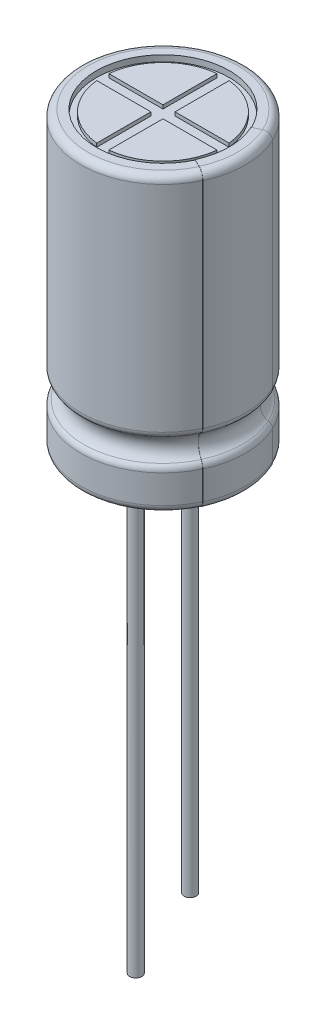
SolidWorks part; units mm, degrees
note: The reader was unsure of these and kept them because the rebuilt part matched: shared geometry of "Sketch7<4>".
ref_plane "Front Plane" through (0, 0, 0) normal (0, 0, 1) x (1, 0, 0)
ref_plane "Top Plane" through (0, 0, 0) normal (0, 1, 0) x (1, 0, 0)
ref_plane "Right Plane" through (0, 0, 0) normal (1, 0, 0) x (0, 0, -1)
sketch "Sketch1" plane through (0, 0, 0) normal (0, 0, 1) x (1, 0, 0)
  line L8 (0, 0.6) -> (2.8, 0.6)
  line L9 (2.8, 0.6) -> (2.8, 0.4)
  line L10 (2.8, 0.4) -> (3.1, 0.4)
  line L11 (3.4, 0.7) -> (3.4, 1.8735)
  line L12 (3.1, 12.5) -> (2.75, 12.5)
  line L13 (2.75, 12.5) -> (2.75, 12.25)
  line L14 (2.75, 12.25) -> (0, 12.25)
  line L15 (0, 12.25) -> (0, 0.6)
  line L16 (1.2518, 2.6) -> (5.492, 2.6) construction
  line L17 (3.4, 3.3265) -> (3.4, 12.2)
  arc A0 (3.1, 0.4) -> (3.4, 0.7) centre (3.1, 0.7) ccw
  arc A1 (3.4, 12.2) -> (3.1, 12.5) centre (3.1, 12.2) ccw
  arc A2 (3.2701, 3.0794) -> (3.2701, 2.1206) centre (3.6, 2.6) ccw
  arc A3 (3.4, 1.8735) -> (3.2701, 2.1206) centre (3.1, 1.8735) ccw
  arc A4 (3.4, 3.3265) -> (3.2701, 3.0794) centre (3.1, 3.3265) cw
  dimension "D8" = 0.3
  dimension "D11" = 1.1639
  dimension "D12" = 0.3
  dimension "D1" = 11.65
  dimension "D2" = 0.2
  dimension "D3" = 0.6
  dimension "D4" = 2.75
  dimension "D5" = 0.65
  dimension "D6" = 0.25
  dimension "D7" = 0.6
  dimension "D9" = 2.2
  dimension "D10" = 3.6
revolve "Revolve1" add sketch "Sketch1" angle 360 about L15
sketch "Sketch2" plane through (0, 12.25, 0) normal (0, 1, 0) x (1, 0, 0)
  line L0 (-0.25, 0.25) -> (-0.25, 2.4875)
  line L2 (0.25, -2.4875) -> (0.25, -0.25)
  line L4 (-0.25, -2.4875) -> (-0.25, -0.25)
  line L5 (0.25, 0.25) -> (0.25, 2.4875)
  line L7 (2.4875, -0.25) -> (0.25, -0.25)
  line L9 (2.4875, 0.25) -> (0.25, 0.25)
  line L13 (-0.25, -0.25) -> (-2.4875, -0.25)
  line L16 (-0.25, 0.25) -> (-2.4875, 0.25)
  arc A0 (0.25, -2.4875) -> (2.4875, -0.25) centre (0, 0) ccw
  arc A1 (2.4875, 0.25) -> (0.25, 2.4875) centre (0, 0) ccw
  arc A2 (-0.25, 2.4875) -> (-2.4875, 0.25) centre (0, 0) ccw
  arc A3 (-2.4875, -0.25) -> (-0.25, -2.4875) centre (0, 0) ccw
  dimension "D3" = 2.5
  dimension "D1" = 0.5
  dimension "D2" = 0.5
extrude "Boss-Extrude1" add sketch "Sketch2" along normal blind 0.15 separate body
sketch "Sketch3" plane through (0, 0.6, 0) normal (0, -1, 0) x (1, 0, 0)
  circle A0 centre (0, 0) radius 1.8
  ellipse E0 centre (0, 0) end of major axis (-1.67, 0) minor radius 0.9
  dimension "D1" = 3.6
extrude "Boss-Extrude2" add sketch "Sketch3" along normal blind 0.6 separate body
sketch "Sketch4" plane through (0, 0.6, 0) normal (0, -1, 0) x (1, 0, 0)
sketch "Sketch5" plane through (0, 0, 0) normal (0, 0, 1) x (1, 0, 0)
  line L8 (2.75, 12.5) -> (3.1, 12.5)
  line L10 (3.4, 3.3265) -> (3.4, 12.2) construction
  line L11 (3.4, 12.2) -> (3.4, 3.3265)
  line L12 (2.75, 12.5) -> (2.8, 0.4)
  line L13 (2.8, 0.4) -> (3.1, 0.4)
  line L14 (0, 0) -> (0, 15.0032) construction
  line L15 (3.41, 12.2) -> (3.41, 3.3265)
  line L16 (3.4, 0.7) -> (3.4, 1.8735)
  line L17 (3.41, 0.7) -> (3.41, 1.8735)
  line L18 (2.79, 0.39) -> (3.1, 0.39)
  line L19 (2.74, 12.51) -> (2.79, 0.39)
  line L20 (2.74, 12.51) -> (3.1, 12.51)
  arc A5 (3.1, 12.5) -> (3.4, 12.2) centre (3.1, 12.2) cw
  arc A6 (3.1, 0.4) -> (3.4, 0.7) centre (3.1, 0.7) ccw construction
  arc A7 (3.4, 1.8735) -> (3.2701, 2.1206) centre (3.1, 1.8735) ccw
  arc A8 (3.4, 3.3265) -> (3.2701, 3.0794) centre (3.1, 3.3265) cw
  arc A9 (3.2701, 3.0794) -> (3.2701, 2.1206) centre (3.6, 2.6) ccw
  arc A10 (3.4, 0.7) -> (3.1, 0.4) centre (3.1, 0.7) cw
  arc A11 (3.1, 12.51) -> (3.41, 12.2) centre (3.1, 12.2) cw
  arc A12 (3.41, 3.3265) -> (3.2757, 3.0712) centre (3.1, 3.3265) cw
  arc A13 (3.2757, 3.0712) -> (3.2757, 2.1288) centre (3.6, 2.6) ccw
  arc A14 (3.41, 1.8735) -> (3.2757, 2.1288) centre (3.1, 1.8735) ccw
  arc A15 (3.41, 0.7) -> (3.1, 0.39) centre (3.1, 0.7) cw
  dimension "D1" = 0.01
revolve "Revolve3" add sketch "Sketch5" angle 25 about L14
sketch "Sketch7" plane through (0, 0.6, 0) normal (0, -1, 0) x (1, 0, 0)
  line L0 (-1.4523, 0) -> (1.4342, 0) construction
  line L1 (0, 0) -> (0, 0.7626) construction
  circle A0 centre (-1.125, 0) radius 0.25
  circle A2 centre (1.125, 0) radius 0.25
  dimension "D2" = 0.5
  dimension "D1" = 1.125
extrude "Boss-Extrude3" add sketch "Sketch7" along normal blind 19.6 contours A0
extrude "Boss-Extrude4" add sketch "Sketch7<4>" along normal blind 15.6 contours A2
sketch "Sketch7<4>" plane through (0, 0.6, 0) normal (0, -1, 0) x (1, 0, 0) same geometry as "Sketch7"
